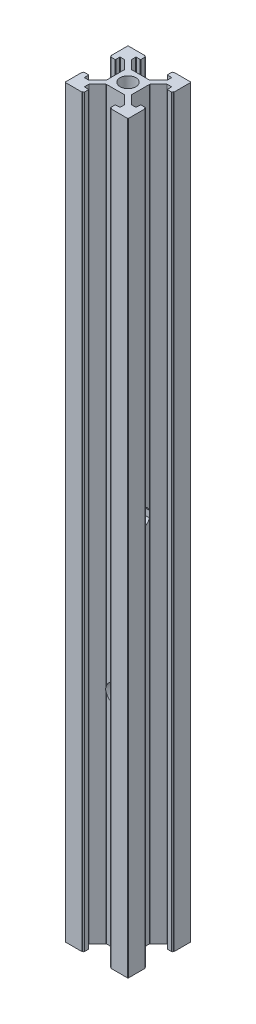
SolidWorks part; units mm, degrees
material "6063-O"
ref_plane "Ön Düzlem" through (0, 0, 0) normal (0, 0, 1) x (1, 0, 0)
ref_plane "Üst Düzlem" through (0, 0, 0) normal (0, 1, 0) x (1, 0, 0)
ref_plane "Sağ Düzlem" through (0, 0, 0) normal (1, 0, 0) x (0, 0, -1)
sketch "Sketch1" plane through (0, 0, 0) normal (0, 1, 0) x (1, 0, 0)
  line L0 (-10, 4.65) -> (-9.8, 4.65)
  line L1 (-9.8, -10) -> (-4.65, -10)
  line L2 (-10, -9.8) -> (-10, -4.65)
  line L3 (-9.8, 10) -> (-4.65, 10)
  line L4 (10, -9.8) -> (10, -4.65)
  line L5 (-10, -10) -> (10, 10) construction
  line L6 (-10, 10) -> (10, -10) construction
  line L7 (-9.8, 4.65) -> (-9.8, 4.4)
  line L8 (-9.6, 4.2) -> (-8.4, 4.2)
  line L9 (-4, 2.8172) -> (-4, -2.8172)
  line L10 (-8.2, 4.4) -> (-8.2, 5.45)
  line L11 (-8, 5.65) -> (-6.8328, 5.65)
  line L12 (-6.6914, 5.5914) -> (-4.0586, 2.9586)
  line L13 (-9.8, -4.65) -> (-10, -4.65)
  line L14 (-6.6914, -5.5914) -> (-4.0586, -2.9586)
  line L15 (-8, -5.65) -> (-6.8328, -5.65)
  line L16 (-8.2, -4.4) -> (-8.2, -5.45)
  line L17 (-9.6, -4.2) -> (-8.4, -4.2)
  line L18 (-9.8, -4.65) -> (-9.8, -4.4)
  line L19 (4.65, 10) -> (4.65, 9.8)
  line L20 (-10, 4.65) -> (-10, 9.8)
  line L21 (4.65, 9.8) -> (4.4, 9.8)
  line L22 (4.2, 9.6) -> (4.2, 8.4)
  line L23 (4.4, 8.2) -> (5.45, 8.2)
  line L24 (5.65, 8) -> (5.65, 6.8328)
  line L25 (5.5914, 6.6914) -> (2.9586, 4.0586)
  line L26 (2.8172, 4) -> (-2.8172, 4)
  line L27 (-5.5914, 6.6914) -> (-2.9586, 4.0586)
  line L28 (-5.65, 8) -> (-5.65, 6.8328)
  line L29 (-4.4, 8.2) -> (-5.45, 8.2)
  line L30 (-4.2, 9.6) -> (-4.2, 8.4)
  line L31 (-4.65, 9.8) -> (-4.4, 9.8)
  line L32 (-4.65, 9.8) -> (-4.65, 10)
  line L33 (10, -4.65) -> (9.8, -4.65)
  line L34 (9.8, -4.65) -> (9.8, -4.4)
  line L35 (9.6, -4.2) -> (8.4, -4.2)
  line L36 (8.2, -4.4) -> (8.2, -5.45)
  line L37 (8, -5.65) -> (6.8328, -5.65)
  line L38 (6.6914, -5.5914) -> (4.0586, -2.9586)
  line L39 (4, -2.8172) -> (4, 2.8172)
  line L40 (6.6914, 5.5914) -> (4.0586, 2.9586)
  line L41 (8, 5.65) -> (6.8328, 5.65)
  line L42 (8.2, 4.4) -> (8.2, 5.45)
  line L43 (9.6, 4.2) -> (8.4, 4.2)
  line L44 (9.8, 4.65) -> (9.8, 4.4)
  line L45 (9.8, 4.65) -> (10, 4.65)
  line L46 (-4.65, -10) -> (-4.65, -9.8)
  line L47 (-4.65, -9.8) -> (-4.4, -9.8)
  line L48 (-4.2, -9.6) -> (-4.2, -8.4)
  line L49 (-4.4, -8.2) -> (-5.45, -8.2)
  line L50 (-5.65, -8) -> (-5.65, -6.8328)
  line L51 (-5.5914, -6.6914) -> (-2.9586, -4.0586)
  line L52 (-2.8172, -4) -> (2.8172, -4)
  line L53 (5.5914, -6.6914) -> (2.9586, -4.0586)
  line L54 (5.65, -8) -> (5.65, -6.8328)
  line L55 (4.4, -8.2) -> (5.45, -8.2)
  line L56 (4.2, -9.6) -> (4.2, -8.4)
  line L57 (4.65, -9.8) -> (4.4, -9.8)
  line L58 (4.65, -9.8) -> (4.65, -10)
  line L59 (4.65, -10) -> (9.8, -10)
  line L60 (10, 4.65) -> (10, 9.8)
  line L61 (4.65, 10) -> (9.8, 10)
  arc A0 (-9.8, 4.4) -> (-9.6, 4.2) centre (-9.6, 4.4) ccw
  arc A1 (-9.8, -4.4) -> (-9.6, -4.2) centre (-9.6, -4.4) cw
  arc A2 (-8.4, 4.2) -> (-8.2, 4.4) centre (-8.4, 4.4) ccw
  arc A3 (-8.2, 5.45) -> (-8, 5.65) centre (-8, 5.45) cw
  arc A4 (-6.6914, 5.5914) -> (-6.8328, 5.65) centre (-6.8328, 5.45) ccw
  arc A5 (-4, 2.8172) -> (-4.0586, 2.9586) centre (-4.2, 2.8172) ccw
  arc A6 (-6.6914, -5.5914) -> (-6.8328, -5.65) centre (-6.8328, -5.45) cw
  arc A7 (-4, -2.8172) -> (-4.0586, -2.9586) centre (-4.2, -2.8172) cw
  arc A8 (-8, -5.65) -> (-8.2, -5.45) centre (-8, -5.45) cw
  arc A9 (-8.2, -4.4) -> (-8.4, -4.2) centre (-8.4, -4.4) ccw
  arc A10 (4.4, 9.8) -> (4.2, 9.6) centre (4.4, 9.6) ccw
  arc A11 (4.2, 8.4) -> (4.4, 8.2) centre (4.4, 8.4) ccw
  arc A12 (5.45, 8.2) -> (5.65, 8) centre (5.45, 8) cw
  arc A13 (5.5914, 6.6914) -> (5.65, 6.8328) centre (5.45, 6.8328) ccw
  arc A14 (2.8172, 4) -> (2.9586, 4.0586) centre (2.8172, 4.2) ccw
  arc A15 (-2.8172, 4) -> (-2.9586, 4.0586) centre (-2.8172, 4.2) cw
  arc A16 (-5.5914, 6.6914) -> (-5.65, 6.8328) centre (-5.45, 6.8328) cw
  arc A17 (-5.65, 8) -> (-5.45, 8.2) centre (-5.45, 8) cw
  arc A18 (-4.4, 8.2) -> (-4.2, 8.4) centre (-4.4, 8.4) ccw
  arc A19 (-4.4, 9.8) -> (-4.2, 9.6) centre (-4.4, 9.6) cw
  arc A20 (9.8, -4.4) -> (9.6, -4.2) centre (9.6, -4.4) ccw
  arc A21 (8.4, -4.2) -> (8.2, -4.4) centre (8.4, -4.4) ccw
  arc A22 (8.2, -5.45) -> (8, -5.65) centre (8, -5.45) cw
  arc A23 (6.6914, -5.5914) -> (6.8328, -5.65) centre (6.8328, -5.45) ccw
  arc A24 (4, -2.8172) -> (4.0586, -2.9586) centre (4.2, -2.8172) ccw
  arc A25 (4, 2.8172) -> (4.0586, 2.9586) centre (4.2, 2.8172) cw
  arc A26 (6.6914, 5.5914) -> (6.8328, 5.65) centre (6.8328, 5.45) cw
  arc A27 (8, 5.65) -> (8.2, 5.45) centre (8, 5.45) cw
  arc A28 (8.2, 4.4) -> (8.4, 4.2) centre (8.4, 4.4) ccw
  arc A29 (9.8, 4.4) -> (9.6, 4.2) centre (9.6, 4.4) cw
  arc A30 (-4.4, -9.8) -> (-4.2, -9.6) centre (-4.4, -9.6) ccw
  arc A31 (-4.2, -8.4) -> (-4.4, -8.2) centre (-4.4, -8.4) ccw
  arc A32 (-5.45, -8.2) -> (-5.65, -8) centre (-5.45, -8) cw
  arc A33 (-5.5914, -6.6914) -> (-5.65, -6.8328) centre (-5.45, -6.8328) ccw
  arc A34 (-2.8172, -4) -> (-2.9586, -4.0586) centre (-2.8172, -4.2) ccw
  arc A35 (2.8172, -4) -> (2.9586, -4.0586) centre (2.8172, -4.2) cw
  arc A36 (5.5914, -6.6914) -> (5.65, -6.8328) centre (5.45, -6.8328) cw
  arc A37 (5.65, -8) -> (5.45, -8.2) centre (5.45, -8) cw
  arc A38 (4.4, -8.2) -> (4.2, -8.4) centre (4.4, -8.4) ccw
  arc A39 (4.4, -9.8) -> (4.2, -9.6) centre (4.4, -9.6) cw
  arc A40 (-9.8, -10) -> (-10, -9.8) centre (-9.8, -9.8) cw
  arc A41 (9.8, -10) -> (10, -9.8) centre (9.8, -9.8) ccw
  arc A42 (10, 9.8) -> (9.8, 10) centre (9.8, 9.8) ccw
  arc A43 (-10, 9.8) -> (-9.8, 10) centre (-9.8, 9.8) cw
  circle A44 centre (0, 0) radius 2.5
  point P0 (0, 0)
  point P12 (-9.8, 4.2)
  point P27 (-9.8, -4.2)
  point P30 (-8.2, 4.2)
  point P33 (-8.2, 5.65)
  point P36 (-6.75, 5.65)
  point P39 (-4, 2.9)
  point P42 (-6.75, -5.65)
  point P45 (-4, -2.9)
  point P48 (-8.2, -5.65)
  point P51 (-8.2, -4.2)
  dimension "D11" = 0.2
  dimension "D13" = 0.2
  dimension "D14" = 5
  dimension "D1" = 20
  dimension "D2" = 20
  dimension "D3" = 5.35
  dimension "D4" = 0.2
  dimension "D5" = 0.45
  dimension "D6" = 1.6
  dimension "D7" = 4.2
  dimension "D8" = 1.45
  dimension "D9" = 1.45
  dimension "D10" = 135
  dimension "D12" = 4
extrude "Boss-Extrude1" add sketch "Sketch1" along normal blind 236
sketch "Sketch2" plane through (4, 0, 0) normal (1, 0, 0) x (0, 0, -1)
  line L0 (0, 236) -> (0, 0)
  line L1 (-2.8172, 236) -> (2.8172, 236) construction
  circle A0 centre (0, 118) radius 3
  line M2 (2.8172, 0) -> (2.8172, 236)
  line M4 (-2.8172, 236) -> (-2.8172, 0)
extrude "Cut-Extrude1" cut sketch "Sketch2" against normal blind 10 and the other way blind 10 contours A0 L0 M2 | L0 A0 M4 region at (4, 118, -1.2438) region at (4, 118, 1.2438)
sketch "Sketch3" plane through (0, 0, 10) normal (0, 0, 1) x (1, 0, 0)
  line L0 (0, 236) -> (0, 0)
  line L1 (-2.8172, 236) -> (2.8172, 236) construction
sketch "Sketch4" plane through (0, 0, 4) normal (0, 0, 1) x (1, 0, 0)
  circle A0 centre (0, 69.881) radius 3
extrude "Cut-Extrude2" cut sketch "Sketch4" against normal blind 10 and the other way blind 10
